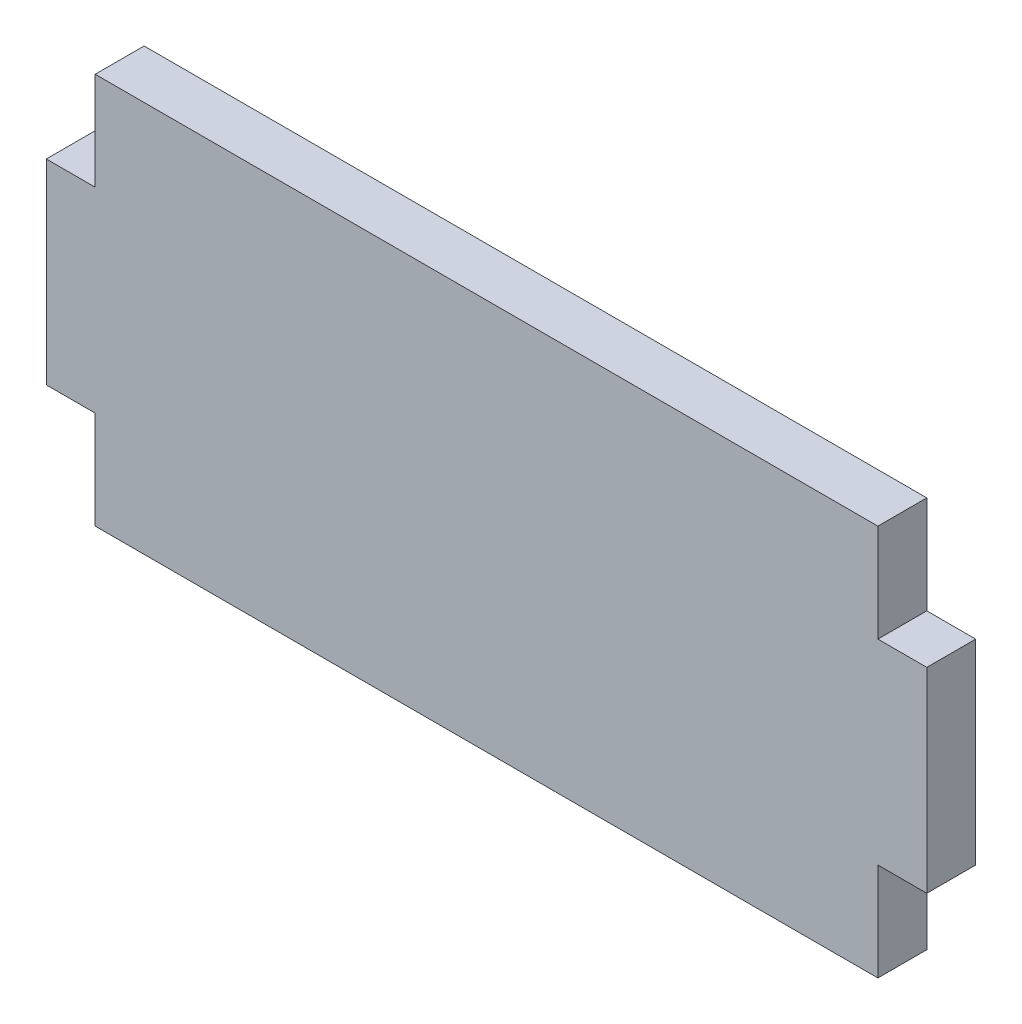
SolidWorks part; units mm, degrees
ref_plane "Front Plane" through (0, 0, 0) normal (0, 0, 1) x (1, 0, 0)
ref_plane "Top Plane" through (0, 0, 0) normal (0, 1, 0) x (1, 0, 0)
ref_plane "Right Plane" through (0, 0, 0) normal (1, 0, 0) x (0, 0, -1)
sketch "Sketch1" plane through (0, 0, 0) normal (0, 0, 1) x (1, 0, 0)
  line L1 (0, 0) -> (50.8, 0)
  line L2 (0, 0) -> (0, 25.4)
  line L3 (0, 25.4) -> (50.8, 25.4)
  line L4 (50.8, 0) -> (50.8, 25.4)
  dimension "D1" = 50.8
  dimension "D2" = 25.4
extrude "Boss-Extrude1" add sketch "Sketch1" along normal blind 3.175
sketch "Sketch2" plane through (0, 0, 3.175) normal (0, 0, 1) x (1, 0, 0)
  line L0 (0, 25.4) -> (0, 0) construction
  line L1 (0, 19.05) -> (-3.175, 19.05)
  line L2 (0, 19.05) -> (0, 6.35)
  line L3 (0, 6.35) -> (-3.175, 6.35)
  line L4 (-3.175, 19.05) -> (-3.175, 6.35)
  line L5 (25.4, 25.4) -> (25.4, 0) construction
  line L6 (50.8, 25.4) -> (0, 25.4) construction
  line L7 (0, 0) -> (50.8, 0) construction
  line L8 (50.8, 6.35) -> (53.975, 6.35)
  line L9 (50.8, 19.05) -> (50.8, 6.35)
  line L10 (50.8, 19.05) -> (53.975, 19.05)
  line L11 (53.975, 19.05) -> (53.975, 6.35)
  point P6 (0, 12.7)
  point P7 (-3.175, 12.7)
  dimension "D1" = 12.7
  dimension "D2" = 3.175
extrude "Boss-Extrude2" add sketch "Sketch2" against normal blind 3.175
